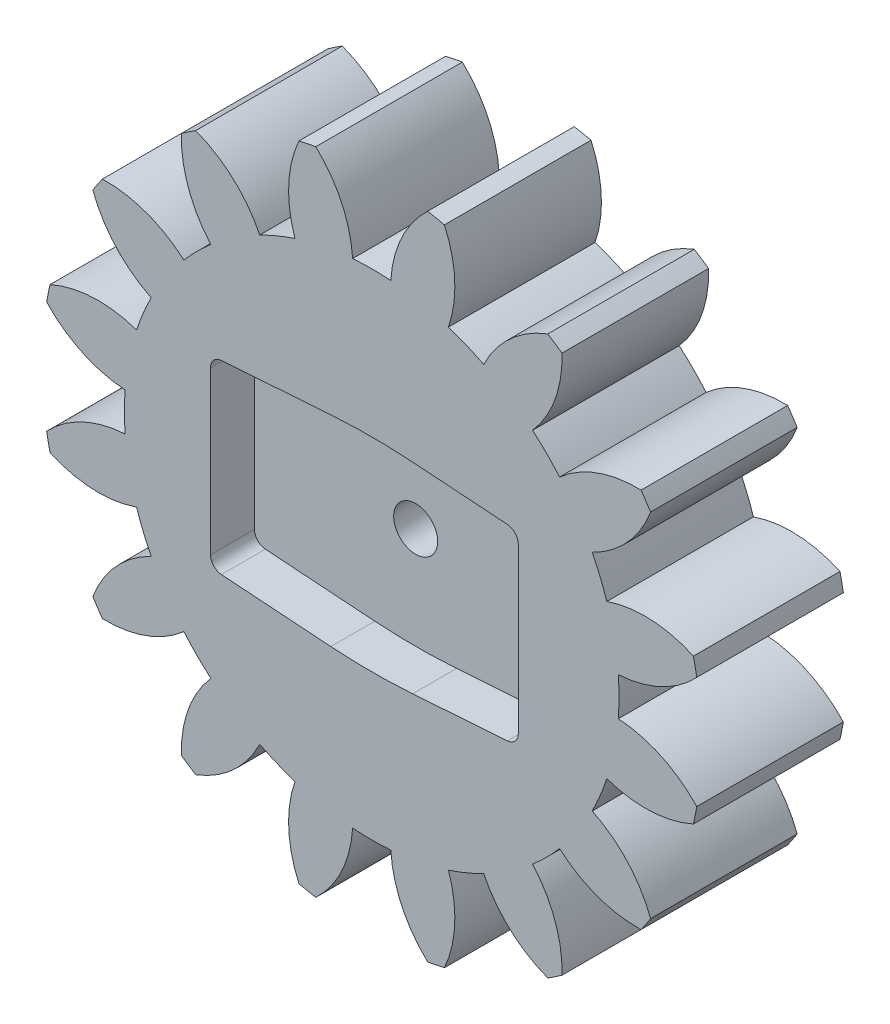
SolidWorks part; units mm, degrees
ref_plane "Alzado" through (0, 0, 0) normal (0, 0, 1) x (1, 0, 0)
ref_plane "Planta" through (0, 0, 0) normal (0, 1, 0) x (1, 0, 0)
ref_plane "Vista lateral" through (0, 0, 0) normal (1, 0, 0) x (0, 0, -1)
sketch "Croquis2" plane through (0, 0, 0) normal (0, 0, 1) x (1, 0, 0)
  circle A0 centre (0, 0) radius 2.5 construction
  circle A1 centre (0, 0) radius 2.5
  circle A2 centre (0, 0) radius 2
  arc A64 (8.4113, 0.6511) -> (11.0871, 1.9076) centre (8.1693, 4.6437) ccw
  arc A65 (11.0871, 1.9076) -> (10.9731, 2.4805) centre (0, 0) ccw
  arc A66 (10.9731, 2.4805) -> (8.0202, 2.6174) centre (9.3246, -1.164) ccw
  arc A67 (8.0202, 2.6174) -> (7.5219, 3.8204) centre (0, 0) ccw
  arc A68 (7.5219, 3.8204) -> (9.5131, 6.0052) centre (5.7704, 7.4165) ccw
  arc A69 (9.5131, 6.0052) -> (9.1886, 6.4909) centre (0, 0) ccw
  arc A70 (9.1886, 6.4909) -> (6.4081, 5.4873) centre (9.0602, 2.493) ccw
  arc A71 (6.4081, 5.4873) -> (5.4873, 6.4081) centre (0, 0) ccw
  arc A72 (5.4873, 6.4081) -> (6.4909, 9.1886) centre (2.493, 9.0602) ccw
  arc A73 (6.4909, 9.1886) -> (6.0052, 9.5131) centre (0, 0) ccw
  arc A74 (6.0052, 9.5131) -> (3.8204, 7.5219) centre (7.4165, 5.7704) ccw
  arc A75 (3.8204, 7.5219) -> (2.6174, 8.0202) centre (0, 0) ccw
  arc A76 (2.6174, 8.0202) -> (2.4805, 10.9731) centre (-1.164, 9.3246) ccw
  arc A77 (2.4805, 10.9731) -> (1.9076, 11.0871) centre (0, 0) ccw
  arc A78 (1.9076, 11.0871) -> (0.6511, 8.4113) centre (4.6437, 8.1693) ccw
  arc A79 (0.6511, 8.4113) -> (-0.6511, 8.4113) centre (0, 0) ccw
  arc A80 (-0.6511, 8.4113) -> (-1.9076, 11.0871) centre (-4.6437, 8.1693) ccw
  arc A81 (-1.9076, 11.0871) -> (-2.4805, 10.9731) centre (0, 0) ccw
  arc A82 (-2.4805, 10.9731) -> (-2.6174, 8.0202) centre (1.164, 9.3246) ccw
  arc A83 (-2.6174, 8.0202) -> (-3.8204, 7.5219) centre (0, 0) ccw
  arc A84 (-3.8204, 7.5219) -> (-6.0052, 9.5131) centre (-7.4165, 5.7704) ccw
  arc A85 (-6.0052, 9.5131) -> (-6.4909, 9.1886) centre (0, 0) ccw
  arc A86 (-6.4909, 9.1886) -> (-5.4873, 6.4081) centre (-2.493, 9.0602) ccw
  arc A87 (-5.4873, 6.4081) -> (-6.4081, 5.4873) centre (0, 0) ccw
  arc A88 (-6.4081, 5.4873) -> (-9.1886, 6.4909) centre (-9.0602, 2.493) ccw
  arc A89 (-9.1886, 6.4909) -> (-9.5131, 6.0052) centre (0, 0) ccw
  arc A90 (-9.5131, 6.0052) -> (-7.5219, 3.8204) centre (-5.7704, 7.4165) ccw
  arc A91 (-7.5219, 3.8204) -> (-8.0202, 2.6174) centre (0, 0) ccw
  arc A92 (-8.0202, 2.6174) -> (-10.9731, 2.4805) centre (-9.3246, -1.164) ccw
  arc A93 (-10.9731, 2.4805) -> (-11.0871, 1.9076) centre (0, 0) ccw
  arc A94 (-11.0871, 1.9076) -> (-8.4113, 0.6511) centre (-8.1693, 4.6437) ccw
  arc A95 (-8.4113, 0.6511) -> (-8.4113, -0.6511) centre (0, 0) ccw
  arc A96 (-8.4113, -0.6511) -> (-11.0871, -1.9076) centre (-8.1693, -4.6437) ccw
  arc A97 (-11.0871, -1.9076) -> (-10.9731, -2.4805) centre (0, 0) ccw
  arc A98 (-10.9731, -2.4805) -> (-8.0202, -2.6174) centre (-9.3246, 1.164) ccw
  arc A99 (-8.0202, -2.6174) -> (-7.5219, -3.8204) centre (0, 0) ccw
  arc A100 (-7.5219, -3.8204) -> (-9.5131, -6.0052) centre (-5.7704, -7.4165) ccw
  arc A101 (-9.5131, -6.0052) -> (-9.1886, -6.4909) centre (0, 0) ccw
  arc A102 (-9.1886, -6.4909) -> (-6.4081, -5.4873) centre (-9.0602, -2.493) ccw
  arc A103 (-6.4081, -5.4873) -> (-5.4873, -6.4081) centre (0, 0) ccw
  arc A104 (-5.4873, -6.4081) -> (-6.4909, -9.1886) centre (-2.493, -9.0602) ccw
  arc A105 (-6.4909, -9.1886) -> (-6.0052, -9.5131) centre (0, 0) ccw
  arc A106 (-6.0052, -9.5131) -> (-3.8204, -7.5219) centre (-7.4165, -5.7704) ccw
  arc A107 (-3.8204, -7.5219) -> (-2.6174, -8.0202) centre (0, 0) ccw
  arc A108 (-2.6174, -8.0202) -> (-2.4805, -10.9731) centre (1.164, -9.3246) ccw
  arc A109 (-2.4805, -10.9731) -> (-1.9076, -11.0871) centre (0, 0) ccw
  arc A110 (-1.9076, -11.0871) -> (-0.6511, -8.4113) centre (-4.6437, -8.1693) ccw
  arc A111 (-0.6511, -8.4113) -> (0.6511, -8.4113) centre (0, 0) ccw
  arc A112 (0.6511, -8.4113) -> (1.9076, -11.0871) centre (4.6437, -8.1693) ccw
  arc A113 (1.9076, -11.0871) -> (2.4805, -10.9731) centre (0, 0) ccw
  arc A114 (2.4805, -10.9731) -> (2.6174, -8.0202) centre (-1.164, -9.3246) ccw
  arc A115 (2.6174, -8.0202) -> (3.8204, -7.5219) centre (0, 0) ccw
  arc A116 (3.8204, -7.5219) -> (6.0052, -9.5131) centre (7.4165, -5.7704) ccw
  arc A117 (6.0052, -9.5131) -> (6.4909, -9.1886) centre (0, 0) ccw
  arc A118 (6.4909, -9.1886) -> (5.4873, -6.4081) centre (2.493, -9.0602) ccw
  arc A119 (5.4873, -6.4081) -> (6.4081, -5.4873) centre (0, 0) ccw
  arc A120 (6.4081, -5.4873) -> (9.1886, -6.4909) centre (9.0602, -2.493) ccw
  arc A121 (9.1886, -6.4909) -> (9.5131, -6.0052) centre (0, 0) ccw
  arc A122 (9.5131, -6.0052) -> (7.5219, -3.8204) centre (5.7704, -7.4165) ccw
  arc A123 (7.5219, -3.8204) -> (8.0202, -2.6174) centre (0, 0) ccw
  arc A124 (8.0202, -2.6174) -> (10.9731, -2.4805) centre (9.3246, 1.164) ccw
  arc A125 (10.9731, -2.4805) -> (11.0871, -1.9076) centre (0, 0) ccw
  arc A126 (11.0871, -1.9076) -> (8.4113, -0.6511) centre (8.1693, -4.6437) ccw
  arc A127 (8.4113, -0.6511) -> (8.4113, 0.6511) centre (0, 0) ccw
  arc A128 (8.4113, 0.6511) -> (11.0871, 1.9076) centre (8.1693, 4.6437) ccw
  arc A129 (11.0871, 1.9076) -> (10.9731, 2.4805) centre (0, 0) ccw
  arc A130 (10.9731, 2.4805) -> (8.0202, 2.6174) centre (9.3246, -1.164) ccw
  arc A131 (8.0202, 2.6174) -> (7.5219, 3.8204) centre (0, 0) ccw
  arc A132 (7.5219, 3.8204) -> (9.5131, 6.0052) centre (5.7704, 7.4165) ccw
  arc A133 (9.5131, 6.0052) -> (9.1886, 6.4909) centre (0, 0) ccw
  arc A134 (9.1886, 6.4909) -> (6.4081, 5.4873) centre (9.0602, 2.493) ccw
  arc A135 (6.4081, 5.4873) -> (5.4873, 6.4081) centre (0, 0) ccw
  arc A136 (5.4873, 6.4081) -> (6.4909, 9.1886) centre (2.493, 9.0602) ccw
  arc A137 (6.4909, 9.1886) -> (6.0052, 9.5131) centre (0, 0) ccw
  arc A138 (6.0052, 9.5131) -> (3.8204, 7.5219) centre (7.4165, 5.7704) ccw
  arc A139 (3.8204, 7.5219) -> (2.6174, 8.0202) centre (0, 0) ccw
  arc A140 (2.6174, 8.0202) -> (2.4805, 10.9731) centre (-1.164, 9.3246) ccw
  arc A141 (2.4805, 10.9731) -> (1.9076, 11.0871) centre (0, 0) ccw
  arc A142 (1.9076, 11.0871) -> (0.6511, 8.4113) centre (4.6437, 8.1693) ccw
  arc A143 (0.6511, 8.4113) -> (-0.6511, 8.4113) centre (0, 0) ccw
  arc A144 (-0.6511, 8.4113) -> (-1.9076, 11.0871) centre (-4.6437, 8.1693) ccw
  arc A145 (-1.9076, 11.0871) -> (-2.4805, 10.9731) centre (0, 0) ccw
  arc A146 (-2.4805, 10.9731) -> (-2.6174, 8.0202) centre (1.164, 9.3246) ccw
  arc A147 (-2.6174, 8.0202) -> (-3.8204, 7.5219) centre (0, 0) ccw
  arc A148 (-3.8204, 7.5219) -> (-6.0052, 9.5131) centre (-7.4165, 5.7704) ccw
  arc A149 (-6.0052, 9.5131) -> (-6.4909, 9.1886) centre (0, 0) ccw
  arc A150 (-6.4909, 9.1886) -> (-5.4873, 6.4081) centre (-2.493, 9.0602) ccw
  arc A151 (-5.4873, 6.4081) -> (-6.4081, 5.4873) centre (0, 0) ccw
  arc A152 (-6.4081, 5.4873) -> (-9.1886, 6.4909) centre (-9.0602, 2.493) ccw
  arc A153 (-9.1886, 6.4909) -> (-9.5131, 6.0052) centre (0, 0) ccw
  arc A154 (-9.5131, 6.0052) -> (-7.5219, 3.8204) centre (-5.7704, 7.4165) ccw
  arc A155 (-7.5219, 3.8204) -> (-8.0202, 2.6174) centre (0, 0) ccw
  arc A156 (-8.0202, 2.6174) -> (-10.9731, 2.4805) centre (-9.3246, -1.164) ccw
  arc A157 (-10.9731, 2.4805) -> (-11.0871, 1.9076) centre (0, 0) ccw
  arc A158 (-11.0871, 1.9076) -> (-8.4113, 0.6511) centre (-8.1693, 4.6437) ccw
  arc A159 (-8.4113, 0.6511) -> (-8.4113, -0.6511) centre (0, 0) ccw
  arc A160 (-8.4113, -0.6511) -> (-11.0871, -1.9076) centre (-8.1693, -4.6437) ccw
  arc A161 (-11.0871, -1.9076) -> (-10.9731, -2.4805) centre (0, 0) ccw
  arc A162 (-10.9731, -2.4805) -> (-8.0202, -2.6174) centre (-9.3246, 1.164) ccw
  arc A163 (-8.0202, -2.6174) -> (-7.5219, -3.8204) centre (0, 0) ccw
  arc A164 (-7.5219, -3.8204) -> (-9.5131, -6.0052) centre (-5.7704, -7.4165) ccw
  arc A165 (-9.5131, -6.0052) -> (-9.1886, -6.4909) centre (0, 0) ccw
  arc A166 (-9.1886, -6.4909) -> (-6.4081, -5.4873) centre (-9.0602, -2.493) ccw
  arc A167 (-6.4081, -5.4873) -> (-5.4873, -6.4081) centre (0, 0) ccw
  arc A168 (-5.4873, -6.4081) -> (-6.4909, -9.1886) centre (-2.493, -9.0602) ccw
  arc A169 (-6.4909, -9.1886) -> (-6.0052, -9.5131) centre (0, 0) ccw
  arc A170 (-6.0052, -9.5131) -> (-3.8204, -7.5219) centre (-7.4165, -5.7704) ccw
  arc A171 (-3.8204, -7.5219) -> (-2.6174, -8.0202) centre (0, 0) ccw
  arc A172 (-2.6174, -8.0202) -> (-2.4805, -10.9731) centre (1.164, -9.3246) ccw
  arc A173 (-2.4805, -10.9731) -> (-1.9076, -11.0871) centre (0, 0) ccw
  arc A174 (-1.9076, -11.0871) -> (-0.6511, -8.4113) centre (-4.6437, -8.1693) ccw
  arc A175 (-0.6511, -8.4113) -> (0.6511, -8.4113) centre (0, 0) ccw
  arc A176 (0.6511, -8.4113) -> (1.9076, -11.0871) centre (4.6437, -8.1693) ccw
  arc A177 (1.9076, -11.0871) -> (2.4805, -10.9731) centre (0, 0) ccw
  arc A178 (2.4805, -10.9731) -> (2.6174, -8.0202) centre (-1.164, -9.3246) ccw
  arc A179 (2.6174, -8.0202) -> (3.8204, -7.5219) centre (0, 0) ccw
  arc A180 (3.8204, -7.5219) -> (6.0052, -9.5131) centre (7.4165, -5.7704) ccw
  arc A181 (6.0052, -9.5131) -> (6.4909, -9.1886) centre (0, 0) ccw
  arc A182 (6.4909, -9.1886) -> (5.4873, -6.4081) centre (2.493, -9.0602) ccw
  arc A183 (5.4873, -6.4081) -> (6.4081, -5.4873) centre (0, 0) ccw
  arc A184 (6.4081, -5.4873) -> (9.1886, -6.4909) centre (9.0602, -2.493) ccw
  arc A185 (9.1886, -6.4909) -> (9.5131, -6.0052) centre (0, 0) ccw
  arc A186 (9.5131, -6.0052) -> (7.5219, -3.8204) centre (5.7704, -7.4165) ccw
  arc A187 (7.5219, -3.8204) -> (8.0202, -2.6174) centre (0, 0) ccw
  arc A188 (8.0202, -2.6174) -> (10.9731, -2.4805) centre (9.3246, 1.164) ccw
  arc A189 (10.9731, -2.4805) -> (11.0871, -1.9076) centre (0, 0) ccw
  arc A190 (11.0871, -1.9076) -> (8.4113, -0.6511) centre (8.1693, -4.6437) ccw
  arc A191 (8.4113, -0.6511) -> (8.4113, 0.6511) centre (0, 0) ccw
  dimension "D2" = 0.5
  dimension "D3" = 9.3969
  dimension "D1" = 0
extrude "Saliente-Extruir1" add sketch "Croquis2" along normal blind 5 contours A190 A191 A128 A129 A130 A131 A132 A133 A134 A135 A136 A137 A138 A139 A140 A141 A142 A143 A144 A145 A146 A147 A148 A149 A150 A151 A152 A153 A154 A155 A156 A157 A158 A159 A160 A161 A162 A163 A164 A165 A166 A167 A168 A169 A170 A171 A172 A173 A174 A175 A176 | A1 region at (8.1229, 0, 0)
sketch "Croquis3"
  line L0 (0, 8.4365) -> (0, -8.4365) construction
  line L1 (0, -8.4365) -> (-8.4365, 0) construction
  line L2 (-8.4365, 0) -> (8.4365, 0) construction
  line L3 (8.4365, 0) -> (0, 8.4365) construction
  line L4 (0, 8.4365) -> (-8.4365, 0) construction
  line L5 (0, -8.4365) -> (8.4365, 0) construction
  line L6 (-5.9655, 5.9655) -> (-5.9655, -5.9655) construction
  line L7 (-5.9655, -5.9655) -> (5.9655, -5.9655) construction
  line L8 (5.9655, -5.9655) -> (5.9655, 5.9655) construction
  line L9 (5.9655, 5.9655) -> (-5.9655, 5.9655) construction
  line L10 (-5.9655, 5.9655) -> (5.9655, -5.9655) construction
  line L11 (5.9655, 5.9655) -> (-5.9655, -5.9655) construction
  arc A0 (3.8204, 7.5219) -> (2.6174, 8.0202) centre (0, 0) ccw construction
  arc A1 (3.8204, 7.5219) -> (2.6174, 8.0202) centre (0, 0) ccw construction
  circle A2 centre (0, 0) radius 2.25
  arc A3 (0.6511, 8.4113) -> (-0.6511, 8.4113) centre (0, 0) ccw construction
  arc A4 (-0.6511, -8.4113) -> (0.6511, -8.4113) centre (0, 0) ccw construction
  arc A5 (-8.4113, 0.6511) -> (-8.4113, -0.6511) centre (0, 0) ccw construction
  arc A6 (8.4113, -0.6511) -> (8.4113, 0.6511) centre (0, 0) ccw construction
  arc A7 (-5.4873, 6.4081) -> (-6.4081, 5.4873) centre (0, 0) ccw construction
  arc A8 (-6.4081, -5.4873) -> (-5.4873, -6.4081) centre (0, 0) ccw construction
  arc A9 (5.4873, -6.4081) -> (6.4081, -5.4873) centre (0, 0) ccw construction
  arc A10 (6.4081, 5.4873) -> (5.4873, 6.4081) centre (0, 0) ccw construction
  circle A11 centre (0, 4.75) radius 0.75
  circle A13 centre (4.75, 0) radius 0.75
  circle A15 centre (0, -4.75) radius 0.75
  circle A17 centre (-4.75, 0) radius 0.75
  circle A27 centre (0, 0) radius 7.2365
  circle A28 centre (0, 0) radius 2.75
  arc A29 (-8.0202, -2.6174) -> (-7.5219, -3.8204) centre (0, 0) ccw construction
  point P40 (0, 2.25)
  dimension "D1" = 4.5
  dimension "D2" = 1.5
  dimension "D7" = 0.5
  dimension "D8" = 1.2
  dimension "D5" = 2.5
  dimension "D6" = 4
sketch "Croquis3<7>" plane through (0, 0, 5) normal (0, 0, 1) x (1, 0, 0) same geometry as "Croquis3"
sketch "Croquis4" plane through (0, 0, 5) normal (0, 0, 1) x (1, 0, 0)
  line L0 (-14.6744, -2.4939) -> (-1.3951, -3.4225)
  line L1 (1.3951, -3.4225) -> (14.6744, -2.4939)
  line L2 (14.6744, 2.4939) -> (1.3951, 3.4225)
  line L3 (-1.3951, 3.4225) -> (-14.6744, 2.4939)
  line L4 (-14.5, 0) -> (14.5, 0) construction
  line L5 (-14.6744, 2.4939) -> (14.6744, 2.4939) construction
  line L6 (-5.5, 3.1354) -> (-5.5, -3.1354)
  line L7 (5, 3.1704) -> (5, -3.1704)
  circle A0 centre (0, 0) radius 1.5
  circle A1 centre (0, 0) radius 0.75
  arc A2 (-1.3951, -3.4225) -> (1.3951, -3.4225) centre (0, 16.5288) ccw
  arc A3 (14.6744, -2.4939) -> (14.6744, 2.4939) centre (14.5, 0) ccw
  arc A4 (1.3951, 3.4225) -> (-1.3951, 3.4225) centre (0, -16.5288) ccw
  arc A5 (-14.6744, 2.4939) -> (-14.6744, -2.4939) centre (-14.5, 0) ccw
  point P17 (0, 3.4712)
  dimension "D1" = 2.5
  dimension "D2" = 20
  dimension "D3" = 1.5
  dimension "D4" = 3
  dimension "D5" = 4
  dimension "D6" = 29
  dimension "D7" = 5.5
  dimension "D8" = 5
extrude "Cortar-Extruir1" cut sketch "Croquis4" against normal up to next contours A1
extrude "Cortar-Extruir2" cut sketch "Croquis4<3>" along normal blind 1.5 from surface contours A0 A1 region at (-1.4576, 0, 5) starting at face at (0.75, 0, 0)
sketch "Croquis4<3>" plane through (0, 0, 5) normal (0, 0, 1) x (1, 0, 0) same geometry as "Croquis4"
extrude "Cortar-Extruir3" cut sketch "Croquis4<4>" against normal blind 1.5 contours A0 A1 | L2 A4 L3 L6 L0 A2 L1 L7 A0 region at (-5.3741, 0, 5) region at (-1.4576, 0, 5)
sketch "Croquis4<4>" plane through (0, 0, 5) normal (0, 0, 1) x (1, 0, 0) same geometry as "Croquis4"
fillet "Redondeo2" radius 0.4 4 edges at (-5.5, -3.1354, 4.25) (-5.5, 3.1354, 4.25) (5, 3.1704, 4.25) (5, -3.1704, 4.25)
